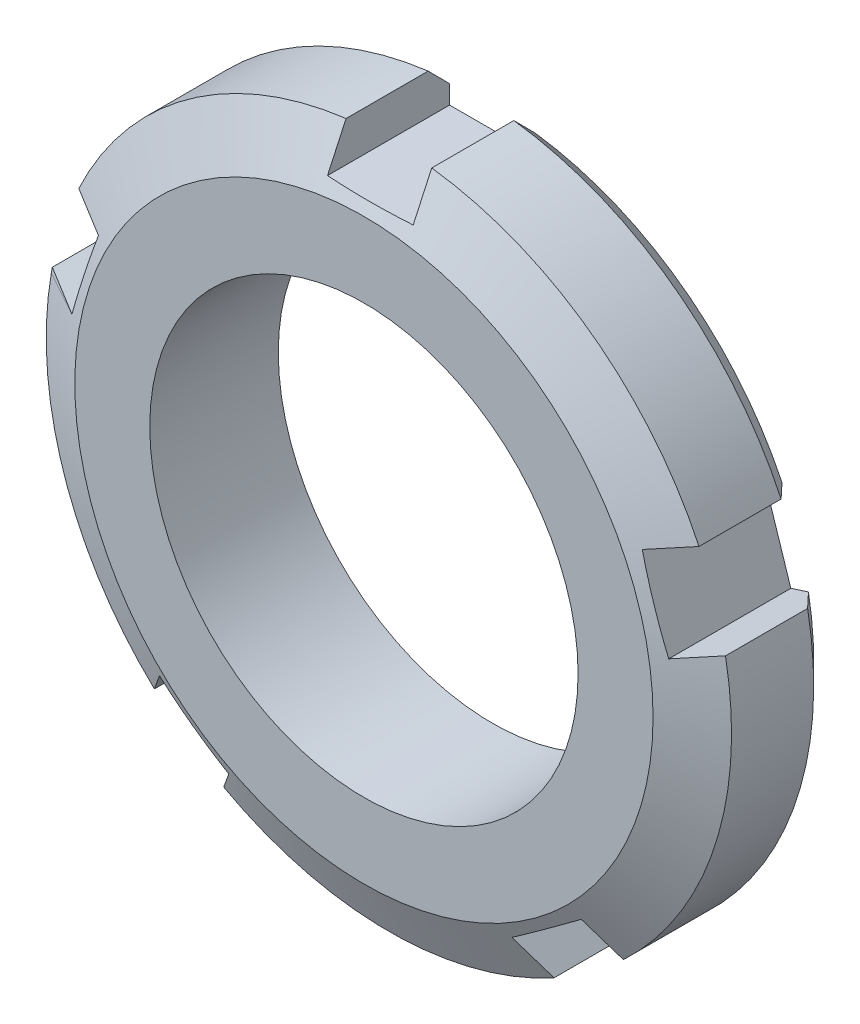
SolidWorks part; units mm, degrees
ref_plane "Front Plane" through (0, 0, 0) normal (0, 0, 1) x (1, 0, 0)
ref_plane "Top Plane" through (0, 0, 0) normal (0, 1, 0) x (1, 0, 0)
ref_plane "Right Plane" through (0, 0, 0) normal (1, 0, 0) x (0, 0, -1)
sketch "Sketch1" plane through (0, 0, 0) normal (1, 0, 0) x (0, 0, -1)
  line L0 (-16.3452, 0) -> (34.4162, 0) construction
  line L1 (0, 10) -> (6, 10)
  line L2 (6, 10) -> (6, 15)
  line L3 (6, 15) -> (5, 16)
  line L4 (5, 16) -> (1.1658, 16)
  line L5 (1.1658, 16) -> (0, 13.5)
  line L6 (0, 13.5) -> (0, 10)
  dimension "D1" = 20
  dimension "D2" = 32
  dimension "D3" = 6
  dimension "D4" = 45
  dimension "D5" = 25
  dimension "D6" = 2.5
  dimension "D7" = 1
revolve "Revolve1" add sketch "Sketch1" angle 360 about L0
sketch "Sketch2" plane through (0, 0, 0) normal (0, 0, 1) x (1, 0, 0)
  line L1 (-2, 16) -> (2, 16)
  line L2 (-2, 16) -> (-2, 14)
  line L3 (-2, 14) -> (2, 14)
  line L4 (2, 16) -> (2, 14)
  circle A0 centre (0, 0) radius 16 construction
  point P4 (0, 14)
  dimension "D1" = 4
  dimension "D2" = 2
extrude "Cut-Extrude1" cut sketch "Sketch2" against normal through all
pattern_circular "CirPattern1" count 5 over 360 about axis through (0, 0, 16.3452) along (0, 0, 1) of "Cut-Extrude1" reverse direction yes
equation "\"D1@Sketch1\"=\"d_int_ecrou_encouch_matrice\""
equation "\"D3@Sketch1\"=\"b_ecrou_encouch_matrice\""
equation "\"D1@Sketch2\"=\"s_ecrou_encouch_matrice\""
equation "\"D2@Sketch2\"=\"s_ecrou_encouch_matrice\"/2"
equation "\"d_ext_rouleau\"= 90"
equation "\"epaisseur_rouleau\"=80"
equation "\"alesage-rouleau\"= 52"
equation "\"jeu_dent_rouleau\"= 2"
equation "\"profondeur_dent_rouleau\"=4"
equation "\"n_dent_roueau\"= 15"
equation "\"d_ext_roulement_rouleau\"= 42"
equation "\"d_int_roulement_rouleau\"= 20"
equation "\"B_roulement_rouleau\"= 12"
equation "\"r_roulement_rouleau\"= 0.6"
equation "\"d_bille_roulement_rouleau\"= 8"
equation "\"F_anneau_alesage_rouleau\"=1.85"
equation "\"G_anneau_alesage_rouleau\"=47.5"
equation "\"K_anneau_alesage_rouleau\"=3.75"
equation "\"d_vis_flasque_rouleau\"=5"
equation "\"l-x_vis_flasque_rouleau\"=4"
equation "\"g_anneau_arbre_rouleau\"=19"
equation "\"f_anneau_arbre_rouleau\"=1.3"
equation "\"k_anneau_arbre_rouleau\"=1.5"
equation "\"h_matrice\"= 22"
equation "\"d_matrice\"= 220"
equation "\"d_granulat\"= 8"
equation "\"zone_vide_matrice\" = 48"
equation "\"d_alesage_matrice\"=20"
equation "\"a_clavette_alesage_matrice\"=6"
equation "\"entrax_vis_rouleau\"=65"
equation "\"B_roulement_matrice\"= 12"
equation "\"d_ext_roulement_matrice\"= 42"
equation "\"d_int_roulement_matrice\"= 20"
equation "\"r_roulement_matrice\"= 1"
equation "\"h_epaulement_arbre_matrice\" = 80"
equation "\"h_polie_matrice\" = 40"
equation "\"l_arbre_matrice\" = 300"
equation "\"d_int_ecrou_encouch_matrice\" = 20"
equation "\"d_ext_ecrou_encouch_matrice\" = 32"
equation "\"b_ecrou_encouch_matrice\" = 6"
equation "\"s_ecrou_encouch_matrice\" = 4"
equation "\"D2@Sketch1\"=\"d_ext_ecrou_encouch_matrice\""
equation "\"G_ecrou_encouch_matrice\" = 1"
equation "\"E_ecrou_encouch_matrice\" = 4"
